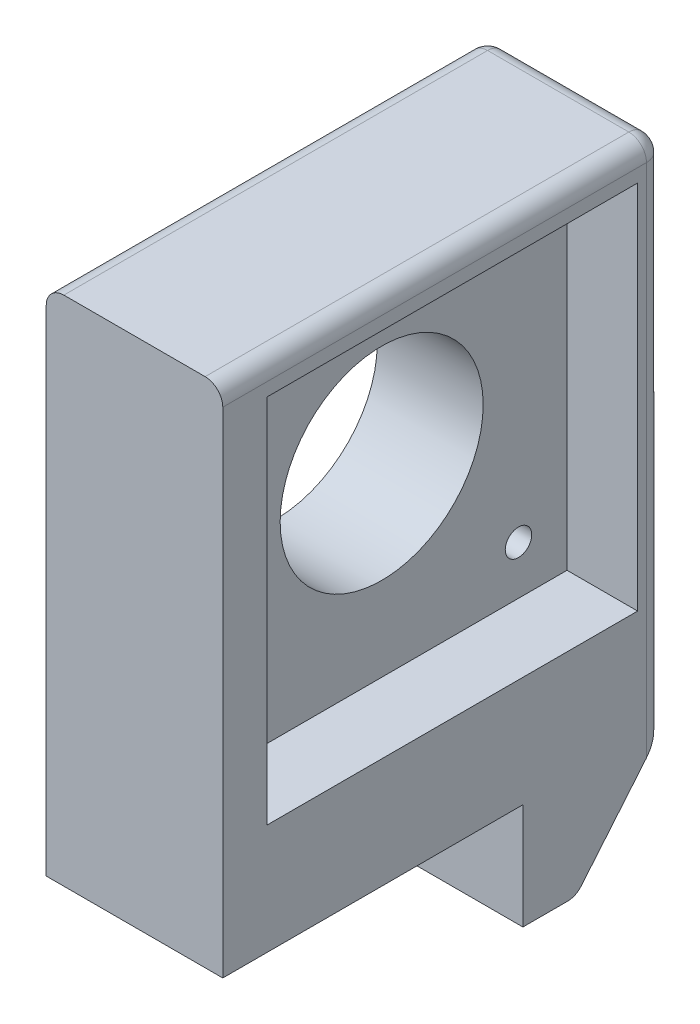
SolidWorks part; units mm, degrees
ref_plane "Front Plane" through (0, 0, 0) normal (0, 0, 1) x (1, 0, 0)
ref_plane "Top Plane" through (0, 0, 0) normal (0, 1, 0) x (1, 0, 0)
ref_plane "Right Plane" through (0, 0, 0) normal (1, 0, 0) x (0, 0, -1)
sketch "Sketch1" plane through (0, 0, 0) normal (0, 1, 0) x (1, 0, 0)
  line L1 (0, 0) -> (-20, 0)
  line L2 (0, 0) -> (0, -50)
  line L3 (0, -50) -> (-20, -50)
  line L4 (-20, 0) -> (-20, -50)
  dimension "D1" = 20
  dimension "D2" = 50
extrude "Boss-Extrude1" add sketch "Sketch1" along normal blind 70
sketch "Sketch2" plane through (0, 0, 0) normal (1, 0, 0) x (0, 0, -1)
  line L0 (-50, 70) -> (0, 70) construction
  line L1 (0, 70) -> (0, 0) construction
  line L2 (0, 45.5) -> (-50, 45.5) construction
  line L3 (-24, 70) -> (-24, 0) construction
  line L4 (-24, 70) -> (-24, 0) construction
  line L5 (-50, 0) -> (0, 0) construction
  line L7 (-50, 70) -> (-50, 0) construction
  circle A0 centre (-8.5, 61) radius 1.5
  circle A4 centre (-24, 45.5) radius 11.5
  circle A5 centre (-8.5, 30) radius 1.5
  circle A8 centre (-39.5, 30) radius 1.5
  circle A9 centre (-39.5, 61) radius 1.5
  point P24 (-25, 0)
  dimension "D1" = 3
  dimension "D2" = 9
  dimension "D3" = 15.5
  dimension "D6" = 23
  dimension "D7" = 0
  dimension "D8" = 0
  dimension "D4" = 15.5
  dimension "D9" = 1
  dimension "D5" = 0
extrude "Cut-Extrude2" cut sketch "Sketch2" against normal blind 60
sketch "Sketch4" plane through (0, 0, 0) normal (1, 0, 0) x (0, 0, -1)
  line L0 (0, 70) -> (0, 0) construction
  line L1 (-50, 0) -> (-16, 0)
  line L2 (-50, 0) -> (-50, 12)
  line L3 (-50, 12) -> (-16, 12)
  line L4 (-16, 0) -> (-16, 12)
  dimension "D1" = 12
  dimension "D2" = 16
extrude "Cut-Extrude3" cut sketch "Sketch4" against normal blind 60
sketch "Sketch8" plane through (0, 0, 0) normal (0, 0, -1) x (-1, 0, 0)
  line L0 (0, 0) -> (20, 0) construction
  line L1 (20, 70) -> (20, 0) construction
  line L2 (0, 70) -> (0, 0) construction
  circle A0 centre (15, 6) radius 2
  circle A1 centre (5, 6) radius 2
  dimension "D1" = 4
  dimension "D2" = 6
  dimension "D3" = 5
  dimension "D4" = 4
  dimension "D5" = 0
  dimension "D6" = 5
extrude "Cut-Extrude5" cut sketch "Sketch8" against normal blind 15
sketch "Sketch9" plane through (0, 0, 0) normal (1, 0, 0) x (0, 0, -1)
  line L0 (0, 49.6538) -> (-50, 41) construction
  line L1 (-3, 66.5) -> (-45, 66.5)
  line L2 (-3, 66.5) -> (-3, 24.5)
  line L3 (-3, 24.5) -> (-45, 24.5)
  line L4 (-45, 66.5) -> (-45, 24.5)
  line L5 (0, 70) -> (0, 0) construction
  line L6 (-50, 70) -> (-50, 12) construction
  line L7 (-24, 70) -> (-24, 12) construction
  line L8 (-50, 70) -> (0, 70) construction
  line L9 (-16, 12) -> (-50, 12) construction
  circle A0 centre (-24, 45.5) radius 11.5 construction
  dimension "D1" = 0
  dimension "D2" = 42
  dimension "D3" = 21
  dimension "D4" = 42
  dimension "D5" = 21
  dimension "D6" = 0
extrude "Cut-Extrude6" cut sketch "Sketch9" against normal blind 8
sketch "Sketch11" plane through (0, 0, 0) normal (1, 0, 0) x (0, 0, -1)
  line L7 (-10, 0) -> (0, 0)
  line L8 (-16, 0) -> (0, 0) construction
  line L9 (0, 0) -> (0, 12)
  line L10 (0, 70) -> (0, 0) construction
  line L11 (0, 12) -> (-10, 0)
  line L12 (-16, 12) -> (-50, 12) construction
  dimension "D1" = 0
  dimension "D2" = 6
extrude "Cut-Extrude8" cut sketch "Sketch11" against normal blind 30
sketch "Sketch17" plane through (0, 0, 0) normal (0, 0, -1) x (-1, 0, 0)
  circle A0 centre (15, 6) radius 3.5
  circle A1 centre (5, 6) radius 3.5
  dimension "D1" = 7
  dimension "D2" = 7
extrude "Cut-Extrude13" cut sketch "Sketch17" against normal blind 9.1811
sketch "Sketch18" plane through (-20, 0, 0) normal (-1, 0, 0) x (0, 0, 1)
  line L0 (50, 70) -> (50, 12) construction
  circle A0 centre (46, 20) radius 1.5
  circle A1 centre (39.5, 30) radius 1.5 construction
  circle A2 centre (39, 20) radius 1.5
  dimension "D1" = 3
  dimension "D2" = 10
  dimension "D3" = 4
  dimension "D4" = 3
  dimension "D5" = 0
  dimension "D6" = 7
extrude "Cut-Extrude14" cut sketch "Sketch18" against normal blind 7
fillet "Fillet1" radius 2 1 edges at (-20, 41, 0)
fillet "Fillet2" radius 2 3 edges at (-9, 70, 0) (-19.4142, 70, 0.5858) (-20, 70, 26)
fillet "Fillet3" radius 2 3 edges at (0, 40, 0) (0, 69.4142, 0.5858) (0, 70, 26)
fillet "Fillet4" radius 2 1 edges at (-10, 0, 10)
